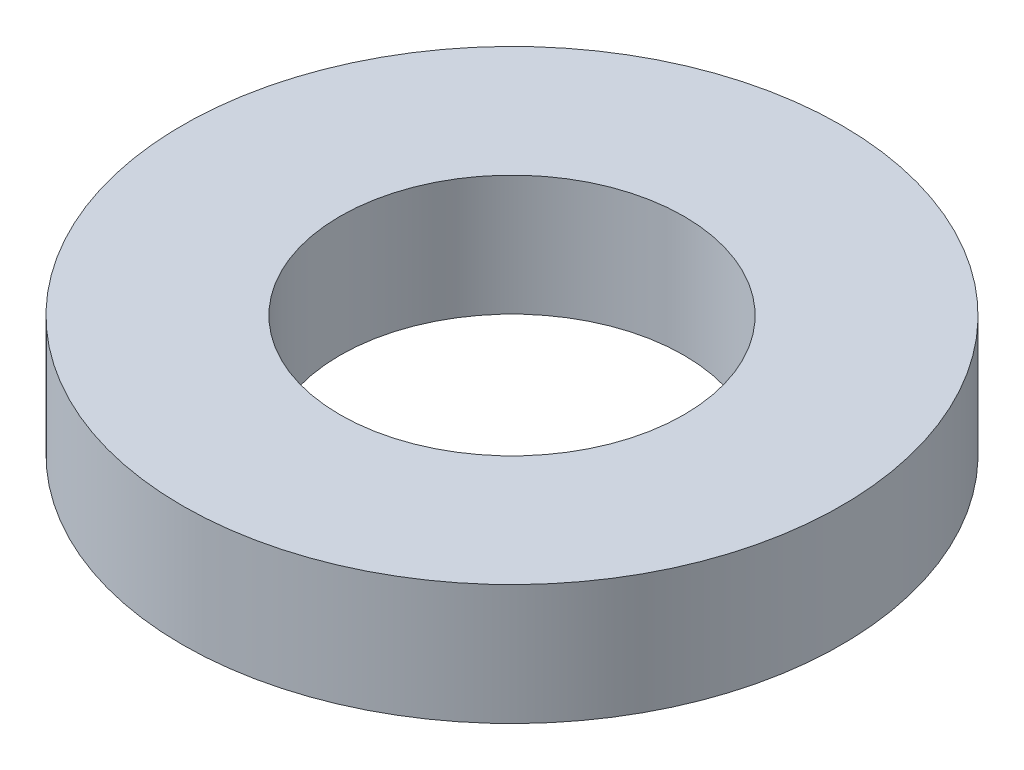
SolidWorks part; units mm, degrees
ref_plane "Front Plane" through (0, 0, 0) normal (0, 0, 1) x (1, 0, 0)
ref_plane "Top Plane" through (0, 0, 0) normal (0, 1, 0) x (1, 0, 0)
ref_plane "Right Plane" through (0, 0, 0) normal (1, 0, 0) x (0, 0, -1)
sketch "Sketch1" plane through (0, 0, 0) normal (0, 1, 0) x (1, 0, 0)
  circle A0 centre (0, 0) radius 57.5
  dimension "FLANGE_OD" = 115
extrude "Boss-Extrude1" add sketch "Sketch1" along normal blind 21
sketch "Sketch2" plane through (0, 0, 0) normal (0, 1, 0) x (1, 0, 0)
  circle A0 centre (0, 0) radius 30
  dimension "BORE_D" = 60
extrude "Cut-Extrude1" cut sketch "Sketch2" along normal through all
sketch "Sketch3" plane through (0, 21, 0) normal (0, 1, 0) x (1, 0, 0)
  circle A0 centre (0, 0) radius 21.2744 construction
  circle A1 centre (-21.2744, 0) radius 4.7064
  dimension "BOLT_D" = 9.4127
  dimension "BOLT_PCD" = 42.5487
extrude "Cut-Extrude2" cut sketch "Sketch3" against normal blind 15.0346 rebuild error yes
pattern_circular "CirPattern1" count 3 over 360 rebuild error yes
